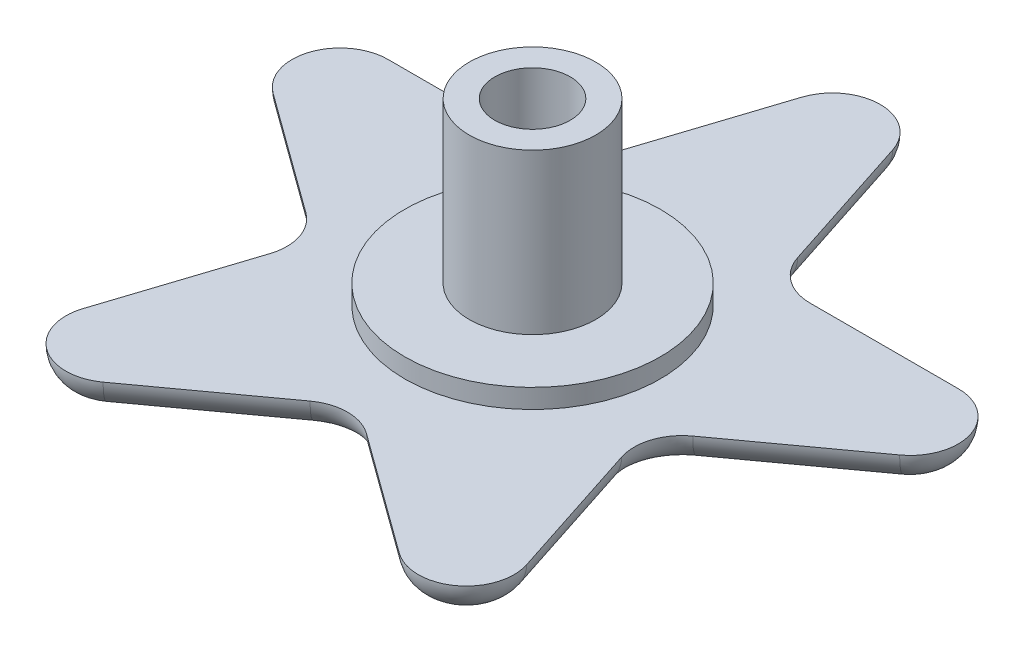
SolidWorks part; units mm, degrees
ref_plane "Alzado" through (0, 0, 0) normal (0, 0, 1) x (1, 0, 0)
ref_plane "Planta" through (0, 0, 0) normal (0, 1, 0) x (1, 0, 0)
ref_plane "Vista lateral" through (0, 0, 0) normal (1, 0, 0) x (0, 0, -1)
sketch "Croquis1" plane through (0, 0, 0) normal (0, 1, 0) x (1, 0, 0)
  line L0 (0, 11) -> (0, -11) construction
  line L1 (-11, 0) -> (11, 0) construction
  line L2 (7.7782, -7.7782) -> (-7.7782, 7.7782) construction
  line L3 (-7.7782, -7.7782) -> (7.7782, 7.7782) construction
  line L7 (0, 11) -> (-10.4616, 3.3992) construction
  line L8 (-10.4616, 3.3992) -> (-6.4656, -8.8992) construction
  line L9 (-6.4656, -8.8992) -> (6.4656, -8.8992) construction
  line L10 (6.4656, -8.8992) -> (10.4616, 3.3992) construction
  line L11 (10.4616, 3.3992) -> (0, 11) construction
  line L19 (1.4266, 9.8455) -> (2.8594, 5.4357)
  line L20 (4.286, 4.3992) -> (8.9228, 4.3992)
  line L21 (9.8045, 1.6857) -> (6.0532, -1.0398)
  line L22 (5.5083, -2.7168) -> (6.9412, -7.1266)
  line L23 (4.6329, -8.8037) -> (0.8817, -6.0783)
  line L24 (-0.8817, -6.0783) -> (-4.6329, -8.8037)
  line L25 (-6.9412, -7.1266) -> (-5.5083, -2.7168)
  line L26 (-6.0532, -1.0398) -> (-9.8045, 1.6857)
  line L27 (-8.9228, 4.3992) -> (-4.286, 4.3992)
  line L28 (-2.8594, 5.4357) -> (-1.4266, 9.8455)
  circle A0 centre (0, 0) radius 11 construction
  circle A1 centre (0, 0) radius 2 construction
  circle A2 centre (0, 0) radius 6.5 construction
  circle A3 centre (0, 0) radius 8.8992 construction
  arc A4 (-5.5083, -2.7168) -> (-6.0532, -1.0398) centre (-6.9349, -2.2533) ccw
  arc A5 (0.8817, -6.0783) -> (-0.8817, -6.0783) centre (0, -7.2918) ccw
  arc A6 (6.0532, -1.0398) -> (5.5083, -2.7168) centre (6.9349, -2.2533) ccw
  arc A7 (2.8594, 5.4357) -> (4.286, 4.3992) centre (4.286, 5.8992) ccw
  arc A8 (-4.286, 4.3992) -> (-2.8594, 5.4357) centre (-4.286, 5.8992) ccw
  arc A9 (-9.8045, 1.6857) -> (-8.9228, 4.3992) centre (-8.9228, 2.8992) cw
  arc A10 (-4.6329, -8.8037) -> (-6.9412, -7.1266) centre (-5.5146, -7.5902) cw
  arc A11 (6.9412, -7.1266) -> (4.6329, -8.8037) centre (5.5146, -7.5902) cw
  arc A12 (8.9228, 4.3992) -> (9.8045, 1.6857) centre (8.9228, 2.8992) cw
  arc A13 (1.4266, 9.8455) -> (-1.4266, 9.8455) centre (0, 9.382) ccw
  dimension "D2" = 1.5
extrude "Saliente-Extruir1" add sketch "Croquis1" along normal blind 1
fillet "Redondeo1" radius 1 20 edges at (-6.2247, 0, 4.9217) (-6.3963, 0, 8.8037) (-2.7573, 0, 7.441) (0, 0, 5.7918) (2.7573, 0, 7.441) (6.3963, 0, 8.8037) (6.2247, 0, 4.9217) (5.5083, 0, 1.7898) (7.9288, 0, -0.3229) (10.3494, 0, -3.3627) (6.6044, 0, -4.3992) (3.4043, 0, -4.6857) (2.143, 0, -7.6406) (0, 0, -10.882) (-2.143, 0, -7.6406) (-3.4043, 0, -4.6857) (-6.6044, 0, -4.3992) (-10.3494, 0, -3.3627) (-7.9288, 0, -0.3229) (-5.5083, 0, 1.7898)
sketch "Croquis5" plane through (0, 1, 0) normal (0, 1, 0) x (1, 0, 0)
  circle A0 centre (0, 0) radius 4
extrude "Saliente-Extruir5" add sketch "Croquis5" along normal blind 0.6
sketch "Croquis2" plane through (0, 1.6, 0) normal (0, 1, 0) x (1, 0, 0)
  circle A0 centre (0, 0) radius 1.98
  circle A1 centre (0, 0) radius 1.18
  dimension "D1" = 0.8
extrude "Saliente-Extruir2" add sketch "Croquis2" along normal blind 5
sketch "Croquis3" [suppressed] plane through (0, 1.6, 0) normal (0, 1, 0) x (1, 0, 0)
  circle A0 centre (0, 0) radius 1.98 construction
  circle A1 centre (0, 0) radius 1.18 construction
  circle A2 centre (0, 0) radius 1.08
  dimension "D1" = 0.8
  dimension "D2" = 0.1
extrude "Saliente-Extruir3" [suppressed] add sketch "Croquis3" along normal blind 5
